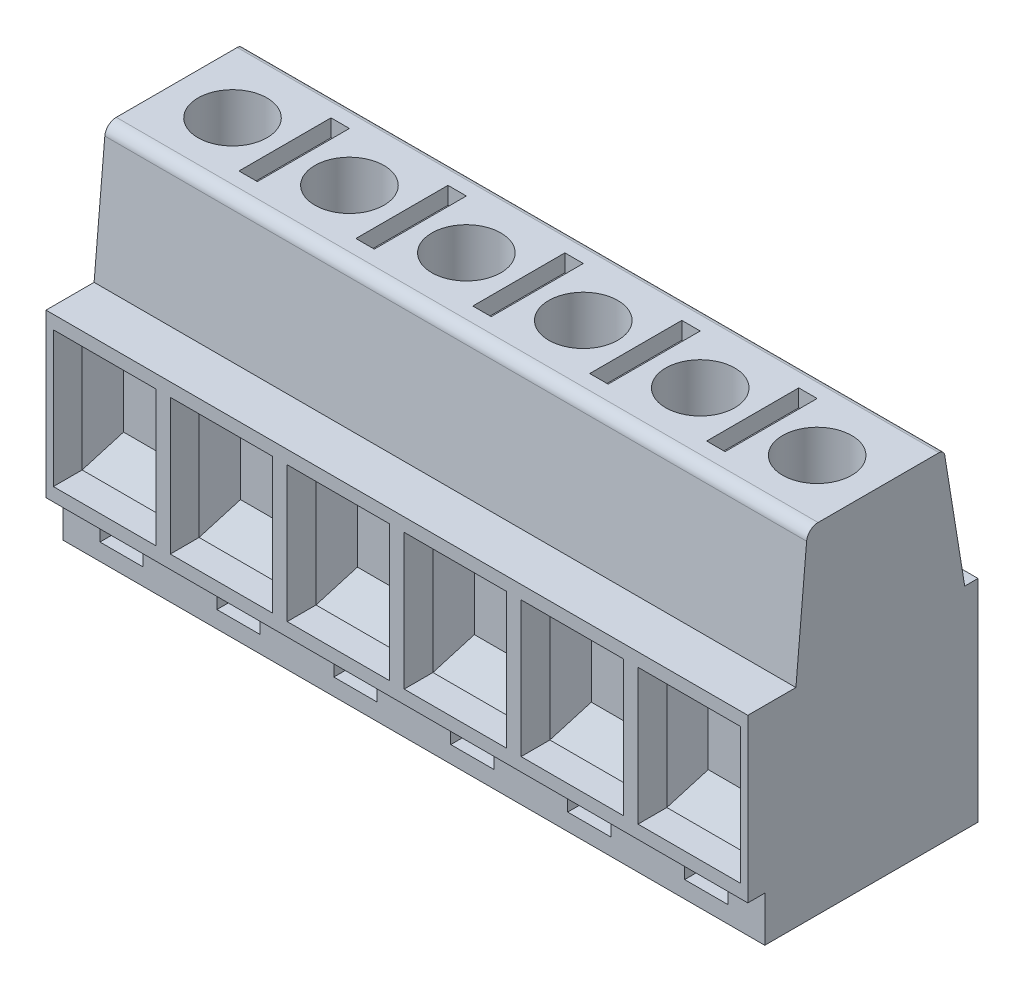
SolidWorks part; units mm, degrees
ref_plane "Front Plane" through (0, 0, 0) normal (0, 0, 1) x (1, 0, 0)
ref_plane "Top Plane" through (0, 0, 0) normal (0, 1, 0) x (1, 0, 0)
ref_plane "Right Plane" through (0, 0, 0) normal (1, 0, 0) x (0, 0, -1)
sketch "Sketch1" plane through (0, 0, 0) normal (1, 0, 0) x (0, 0, -1)
  line L0 (9.6447, 33.3244) -> (29.6447, 33.3244) construction
  line L1 (9.6692, 32.9692) -> (9.6692, 47.0868)
  line L2 (9.6692, 47.0868) -> (13.8475, 47.0868)
  line L3 (13.8475, 47.0868) -> (14.8593, 58.5419)
  line L4 (14.8593, 58.5419) -> (26.709, 58.5419)
  line L5 (26.709, 58.5419) -> (28.5149, 47.3865)
  line L6 (28.5149, 47.3865) -> (29.6692, 47.3865)
  line L7 (29.6692, 47.3865) -> (29.6692, 29.0419)
  line L8 (29.6692, 29.0419) -> (11.1423, 29.0419)
  line L9 (11.1423, 29.0419) -> (11.1423, 32.9692)
  line L10 (11.1423, 32.9692) -> (9.6692, 32.9692)
  line L11 (68.0457, 60.9618) -> (149.3457, 60.9618) construction
  line L12 (139.8559, 49.112) -> (148.7559, 49.112) construction
  line L13 (139.8559, 49.112) -> (139.8559, 37.312) construction
  line L14 (204.1416, 49.112) -> (206.6416, 49.112) construction
  line L15 (208.5587, 45.7504) -> (208.5587, 39.4578) construction
  line L16 (208.5587, 42.6041) -> (206.6416, 42.6041) construction
  line L17 (121.2763, 41.7533) -> (126.7736, 41.7533) construction
  line L18 (217.6919, 61.8593) -> (217.6919, 56.1569) construction
  line L19 (142.8406, 99.3741) -> (145.9297, 99.3741) construction
  line L20 (211.5813, 61.8593) -> (211.5813, 60.3558) construction
  line L21 (118.1896, 87.8673) -> (119.7969, 87.8673) construction
  line L22 (118.1896, 87.8673) -> (118.1896, 95.8627) construction
  line L23 (118.1896, 95.8627) -> (119.7969, 95.8627) construction
  line L24 (119.7969, 87.8673) -> (119.7969, 95.8627) construction
  line L25 (170.4098, 32.3653) -> (173.8098, 32.3653) construction
  line L26 (173.8098, 32.3653) -> (175.1098, 32.3653) construction
  line L27 (175.1098, 32.3653) -> (178.3098, 32.3653) construction
  line L28 (178.3098, 32.3653) -> (179.6098, 32.3653) construction
  line L29 (179.6098, 32.3653) -> (183.0098, 32.3653) construction
  line L30 (183.0098, 32.3653) -> (184.3098, 32.3653) construction
  line L31 (142.4541, 34.5696) -> (146.1866, 34.5696) construction
  line L32 (146.1866, 34.5696) -> (142.4541, 34.5696) construction
  line L33 (142.4541, 34.5696) -> (142.4541, 33.584) construction
  circle A0 centre (134.2519, 91.3377) radius 3.0186 construction
  dimension "D1" = 20
  dimension "D2" = 20
  dimension "D3" = 29.5
  dimension "D4" = 9.6692
  dimension "D5" = 11.1423
  dimension "D6" = 13.8475
  dimension "D7" = 14.8593
  dimension "D8" = 26.709
  dimension "D9" = 28.5149
  dimension "D10" = 29.0419
  dimension "D11" = 32.9692
  dimension "D12" = 33.3244
  dimension "D13" = 47.0868
  dimension "D14" = 47.3865
  dimension "D15" = 81.3
  dimension "D16" = 8.9
  dimension "D17" = 11.8
  dimension "D18" = 2.5
  dimension "D19" = 1.6073
  dimension "D20" = 7.9954
  dimension "D21" = 3.4
  dimension "D22" = 1.3
  dimension "D23" = 3.2
  dimension "D24" = 1.3
  dimension "D25" = 3.4
  dimension "D26" = 1.3
extrude "Boss-Extrude1" add sketch "Sketch1" along normal blind 10.16
sketch "Sketch2" plane through (0, 0, -9.6692) normal (0, 0, 1) x (1, 0, 0)
  line L0 (0, 47.0868) -> (0, 32.9692) construction
  line L1 (0.63, 34.128) -> (9.53, 34.128)
  line L2 (0.63, 34.128) -> (0.63, 45.928)
  line L3 (0.63, 45.928) -> (9.53, 45.928)
  line L4 (9.53, 34.128) -> (9.53, 45.928)
  line L5 (0.63, 34.128) -> (9.53, 45.928) construction
  line L6 (0.63, 45.928) -> (9.53, 34.128) construction
  line L7 (10.16, 47.0868) -> (0, 47.0868) construction
  point P0 (5.08, 40.028)
  point P5 (0, 0)
  point P8 (0, 40.028)
  point P9 (0, 0)
  point P12 (5.08, 47.0868)
  point P13 (9.3089, 45.6013)
  dimension "D1" = 8.9
  dimension "D2" = 11.8
extrude "Cut-Extrude1" cut sketch "Sketch2" against normal blind 2.5
sketch "Sketch3" plane through (0, 0, -12.1692) normal (0, 0, 1) x (1, 0, 0)
  line L4 (9.53, 34.128) -> (9.53, 45.928)
  line L5 (9.53, 45.928) -> (0.63, 45.928)
  line L6 (0.63, 45.928) -> (0.63, 34.128)
  line L7 (0.63, 34.128) -> (9.53, 34.128)
  line L8 (9.53, 34.128) -> (9.53, 45.928)
  line L9 (9.53, 45.928) -> (0.63, 45.928)
  line L10 (0.63, 45.928) -> (0.63, 34.128)
  line L11 (0.63, 34.128) -> (9.53, 34.128)
  dimension "D1" = 0
ref_plane "Plane1" through (0, 0, -14.0692) normal (0, 0, 1) x (1, 0, 0)
sketch "Sketch4" plane through (0, 0, -14.0692) normal (0, 0, 1) x (1, 0, 0)
  line L0 (9.53, 45.928) -> (0.63, 45.928) construction
  line L1 (2.33, 36.878) -> (7.83, 36.878)
  line L2 (2.33, 36.878) -> (2.33, 43.178)
  line L3 (2.33, 43.178) -> (7.83, 43.178)
  line L4 (7.83, 36.878) -> (7.83, 43.178)
  line L5 (2.33, 36.878) -> (7.83, 43.178) construction
  line L6 (2.33, 43.178) -> (7.83, 36.878) construction
  line L7 (0.63, 45.928) -> (0.63, 34.128) construction
  point P0 (5.08, 40.028)
  point P5 (0, 0)
  point P8 (5.08, 45.928)
  point P9 (0, 0)
  point P12 (0.63, 40.028)
  dimension "D1" = 6.3
  dimension "D2" = 5.5
loft "Cut-Loft1" cut profiles "Sketch3", "Sketch4" connector at (0.63, 45.928, -12.1692) connector at (2.33, 43.178, -14.0692)
sketch "Sketch5" plane through (0, 58.5419, 0) normal (0, 1, 0) x (1, 0, 0)
  line L0 (10.16, 26.709) -> (10.16, 14.8593) construction
  line L1 (10.16, 29.6692) -> (0, 29.6692) construction
  circle A0 centre (5.08, 20.7842) radius 3
  point P2 (0, 0)
  point P5 (10.16, 20.7842)
  point P6 (0, 0)
  point P9 (5.08, 29.6692)
  dimension "D1" = 6
extrude "Cut-Extrude2" cut sketch "Sketch5" against normal blind 5.7
sketch "Sketch7" plane through (0, 29.0419, 0) normal (0, -1, 0) x (1, 0, 0)
  line L0 (10.16, -11.1423) -> (0, -11.1423) construction
  line L1 (4.43, -27.5692) -> (5.73, -27.5692)
  line L2 (4.43, -27.5692) -> (4.43, -26.7692)
  line L3 (4.43, -26.7692) -> (5.73, -26.7692)
  line L4 (5.73, -27.5692) -> (5.73, -26.7692)
  line L5 (4.43, -27.5692) -> (5.73, -26.7692) construction
  line L6 (4.43, -26.7692) -> (5.73, -27.5692) construction
  line L7 (4.43, -17.4092) -> (5.73, -17.4092)
  line L8 (4.43, -17.4092) -> (4.43, -16.6092)
  line L9 (4.43, -16.6092) -> (5.73, -16.6092)
  line L10 (5.73, -17.4092) -> (5.73, -16.6092)
  line L11 (4.43, -17.4092) -> (5.73, -16.6092) construction
  line L12 (4.43, -16.6092) -> (5.73, -17.4092) construction
  line L13 (10.16, -29.6692) -> (0, -29.6692) construction
  point P0 (5.08, -27.1692)
  point P5 (5.08, -17.0092)
  point P10 (0, 0)
  point P13 (5.08, -11.1423)
  dimension "D1" = 1.3
  dimension "D2" = 0.8
  dimension "D3" = 2.5
  dimension "D4" = 10.16
extrude "Boss-Extrude2" add sketch "Sketch7" along normal blind 4.5
sketch "Sketch8" plane through (0, 0, -16.6092) normal (0, 0, 1) x (1, 0, 0)
  line L0 (4.43, 24.5419) -> (4.43, 29.0419) construction
  line L1 (5.73, 24.5419) -> (5.73, 29.0419) construction
  line L2 (5.73, 24.5419) -> (4.43, 24.5419) construction
  arc A0 (4.43, 25.1919) -> (5.73, 25.1919) centre (5.08, 25.1919) ccw
  point P3 (5.08, 24.5419)
extrude "Cut-Extrude5" cut sketch "Sketch8" against normal through all flip side to cut
ref_plane "Plane2" through (0, 38.5279, -38.5279) normal (0, 0.7071, -0.7071) x (-1, 0, 0)
sketch "Sketch10" plane through (0, 38.5279, -38.5279) normal (0, 0.7071, -0.7071) x (-1, 0, 0)
  line L0 (-10.16, 12.528) -> (0, 12.528) construction
  circle A0 centre (-5.08, 12.528) radius 1.5
  dimension "D1" = 3
extrude "Cut-Extrude6" cut sketch "Sketch10" against normal blind 4.5 contours A0
sketch "Sketch13" plane through (0, 0, -11.1423) normal (0, 0, 1) x (1, 0, 0)
  line L0 (10.16, 32.9692) -> (10.16, 29.0419) construction
  line L1 (3.205, 30.5055) -> (6.955, 30.5055)
  line L2 (3.205, 30.5055) -> (3.205, 31.5055)
  line L3 (3.205, 31.5055) -> (6.955, 31.5055)
  line L4 (6.955, 30.5055) -> (6.955, 31.5055)
  line L5 (3.205, 30.5055) -> (6.955, 31.5055) construction
  line L6 (3.205, 31.5055) -> (6.955, 30.5055) construction
  line L7 (10.16, 32.9692) -> (0, 32.9692) construction
  point P0 (5.08, 31.0055)
  point P5 (0, 0)
  point P8 (10.16, 31.0055)
  point P9 (0, 0)
  point P12 (5.08, 32.9692)
  dimension "D1" = 3.75
  dimension "D2" = 1
extrude "Cut-Extrude8" cut sketch "Sketch13" against normal blind 3
fillet "Fillet3" radius 0.5 1 edges at (5.08, 58.5419, -26.709) type face fillet first side face at (5.08, 58.5419, -17.7842) second side face at (5.08, 51.2437, -27.8905)
fillet "Fillet4" radius 1 1 edges at (5.08, 58.5419, -14.8593) type face fillet first side face at (5.08, 58.5419, -17.7842) second side face at (5.08, 52.8143, -14.3534)
sketch "Sketch12" plane through (0, 29.0419, 0) normal (0, -1, 0) x (1, 0, 0)
  line L1 (-0.65, -15.8423) -> (0.65, -15.8423)
  line L2 (-0.65, -15.8423) -> (-0.65, -14.5423)
  line L3 (-0.65, -14.5423) -> (0.65, -14.5423)
  line L4 (0.65, -15.8423) -> (0.65, -14.5423)
  line L5 (-0.65, -15.8423) -> (0.65, -14.5423) construction
  line L6 (-0.65, -14.5423) -> (0.65, -15.8423) construction
  line L8 (-0.65, -20.3423) -> (0.65, -20.3423)
  line L9 (-0.65, -20.3423) -> (-0.65, -19.0423)
  line L10 (-0.65, -19.0423) -> (0.65, -19.0423)
  line L11 (0.65, -20.3423) -> (0.65, -19.0423)
  line L12 (-0.65, -20.3423) -> (0.65, -19.0423) construction
  line L13 (-0.65, -19.0423) -> (0.65, -20.3423) construction
  line L14 (-0.65, -25.0423) -> (0.65, -25.0423)
  line L15 (-0.65, -25.0423) -> (-0.65, -23.7423)
  line L16 (-0.65, -23.7423) -> (0.65, -23.7423)
  line L17 (0.65, -25.0423) -> (0.65, -23.7423)
  line L18 (-0.65, -25.0423) -> (0.65, -23.7423) construction
  line L19 (-0.65, -23.7423) -> (0.65, -25.0423) construction
  line L20 (10.16, -11.1423) -> (0, -11.1423) construction
  line L21 (0, -11.1423) -> (0, -29.6692) construction
  point P0 (0, -15.1923)
  point P5 (0, 0)
  point P6 (0, -15.1923)
  point P7 (0, -19.6923)
  point P12 (0, -24.3923)
  point P21 (0, 0)
  point P22 (0, 0)
  point P23 (0, -15.1923)
  point P24 (0, -19.6923)
  point P25 (0, -24.3923)
  dimension "D1" = 3.4
  dimension "D2" = 1.3
  dimension "D3" = 3.2
  dimension "D4" = 3.4
  dimension "D5" = 1.3
extrude "Boss-Extrude3" add sketch "Sketch12" along normal blind 0.5 separate body
sketch "Sketch14" plane through (10.16, 0, 0) normal (1, 0, 0) x (0, 0, -1)
  line L10 (26.2835, 58.5419) -> (15.7749, 58.5419)
  line L11 (14.7788, 57.6298) -> (13.8475, 47.0868)
  line L12 (13.8475, 47.0868) -> (9.6692, 47.0868)
  line L13 (9.6692, 47.0868) -> (9.6692, 32.9692)
  line L14 (9.6692, 32.9692) -> (11.1423, 32.9692)
  line L15 (11.1423, 32.9692) -> (11.1423, 29.0419)
  line L16 (11.1423, 29.0419) -> (29.6692, 29.0419)
  line L17 (29.6692, 29.0419) -> (29.6692, 47.3865)
  line L18 (29.6692, 47.3865) -> (28.5149, 47.3865)
  line L19 (28.5149, 47.3865) -> (26.777, 58.1218)
  line L21 (14.7788, 57.6298) -> (13.8475, 47.0868)
  line L22 (13.8475, 47.0868) -> (9.6692, 47.0868)
  line L23 (9.6692, 47.0868) -> (9.6692, 32.9692)
  line L24 (9.6692, 32.9692) -> (11.1423, 32.9692)
  line L25 (11.1423, 32.9692) -> (11.1423, 29.0419)
  line L26 (11.1423, 29.0419) -> (29.6692, 29.0419)
  line L27 (29.6692, 29.0419) -> (29.6692, 47.3865)
  line L28 (29.6692, 47.3865) -> (28.5149, 47.3865)
  line L29 (28.5149, 47.3865) -> (26.777, 58.1218)
  line L31 (26.2835, 58.5419) -> (15.7749, 58.5419)
  arc A3 (26.777, 58.1218) -> (26.2835, 58.5419) centre (26.2835, 58.0419) ccw
  arc A6 (26.777, 58.1218) -> (26.2835, 58.5419) centre (26.2835, 58.0419) ccw
  arc A8 (15.7749, 58.5419) -> (14.7788, 57.6298) centre (15.7749, 57.5419) ccw
  arc A9 (15.7749, 58.5419) -> (14.7788, 57.6298) centre (15.7749, 57.5419) ccw
  dimension "D1" = 0
extrude "Boss-Extrude4" add sketch "Sketch14" along normal blind 0.01
ref_plane "Plane3" through (0, 0, 0) normal (-1, 0, 0) x (0, 0, 1)
pattern_linear "LPattern8" count 6 spacing 10.16 along (-1, 0, 0) of "Boss-Extrude1", "Cut-Extrude1", "Cut-Loft1", "Cut-Extrude2", "Boss-Extrude2", "Cut-Extrude5", "Cut-Extrude6", "Cut-Extrude8", "Fillet3", "Fillet4"
sketch "Sketch11" plane through (0, 58.5419, 0) normal (0, 1, 0) x (1, 0, 0)
  line L1 (-0.8, 17.0641) -> (0.8, 17.0641)
  line L2 (-0.8, 17.0641) -> (-0.8, 25.0641)
  line L3 (-0.8, 25.0641) -> (0.8, 25.0641)
  line L4 (0.8, 17.0641) -> (0.8, 25.0641)
  line L5 (-0.8, 17.0641) -> (0.8, 25.0641) construction
  line L6 (-0.8, 25.0641) -> (0.8, 17.0641) construction
  line L8 (0, 55) -> (0, -55) construction
  point P0 (0, 21.0641)
  point P5 (1.8522, 20.6032)
  point P6 (1.6707, 20.773)
  point P7 (0, 0)
  point P8 (0, 0)
  point P12 (0, 0)
  point P13 (0.3317, 21.0641)
  point P16 (0, 0)
  dimension "D1" = 1.6
  dimension "D2" = 8
extrude "Cut-Extrude7" cut sketch "Sketch11" against normal blind 1.5
pattern_linear "LPattern9" count 5 spacing 10.16 along (-1, 0, 0) of "Boss-Extrude3", "Cut-Extrude7"
sketch "Sketch16" plane through (-50.8, 0, 0) normal (-1, 0, 0) x (0, 0, 1)
  line L10 (-13.8475, 47.0868) -> (-14.7788, 57.6298)
  line L11 (-15.7749, 58.5419) -> (-26.2835, 58.5419)
  line L12 (-26.777, 58.1218) -> (-28.5149, 47.3865)
  line L13 (-28.5149, 47.3865) -> (-29.6692, 47.3865)
  line L14 (-29.6692, 47.3865) -> (-29.6692, 29.0419)
  line L15 (-29.6692, 29.0419) -> (-11.1423, 29.0419)
  line L16 (-11.1423, 29.0419) -> (-11.1423, 32.9692)
  line L17 (-11.1423, 32.9692) -> (-9.6692, 32.9692)
  line L18 (-9.6692, 32.9692) -> (-9.6692, 47.0868)
  line L19 (-9.6692, 47.0868) -> (-13.8475, 47.0868)
  line L72 (-13.8475, 47.0868) -> (-14.7788, 57.6298)
  line L73 (-15.7749, 58.5419) -> (-26.2835, 58.5419)
  line L74 (-26.777, 58.1218) -> (-28.5149, 47.3865)
  line L75 (-28.5149, 47.3865) -> (-29.6692, 47.3865)
  line L76 (-29.6692, 47.3865) -> (-29.6692, 29.0419)
  line L77 (-29.6692, 29.0419) -> (-11.1423, 29.0419)
  line L78 (-11.1423, 29.0419) -> (-11.1423, 32.9692)
  line L79 (-11.1423, 32.9692) -> (-9.6692, 32.9692)
  line L80 (-9.6692, 32.9692) -> (-9.6692, 47.0868)
  line L81 (-9.6692, 47.0868) -> (-13.8475, 47.0868)
  arc A2 (-14.7788, 57.6298) -> (-15.7749, 58.5419) centre (-15.7749, 57.5419) ccw
  arc A8 (-26.2835, 58.5419) -> (-26.777, 58.1218) centre (-26.2835, 58.0419) ccw
  arc A16 (-14.7788, 57.6298) -> (-15.7749, 58.5419) centre (-15.7749, 57.5419) ccw
  arc A17 (-26.2835, 58.5419) -> (-26.777, 58.1218) centre (-26.2835, 58.0419) ccw
  dimension "D1" = 0
extrude "Boss-Extrude6" add sketch "Sketch16" along normal blind 0.01
